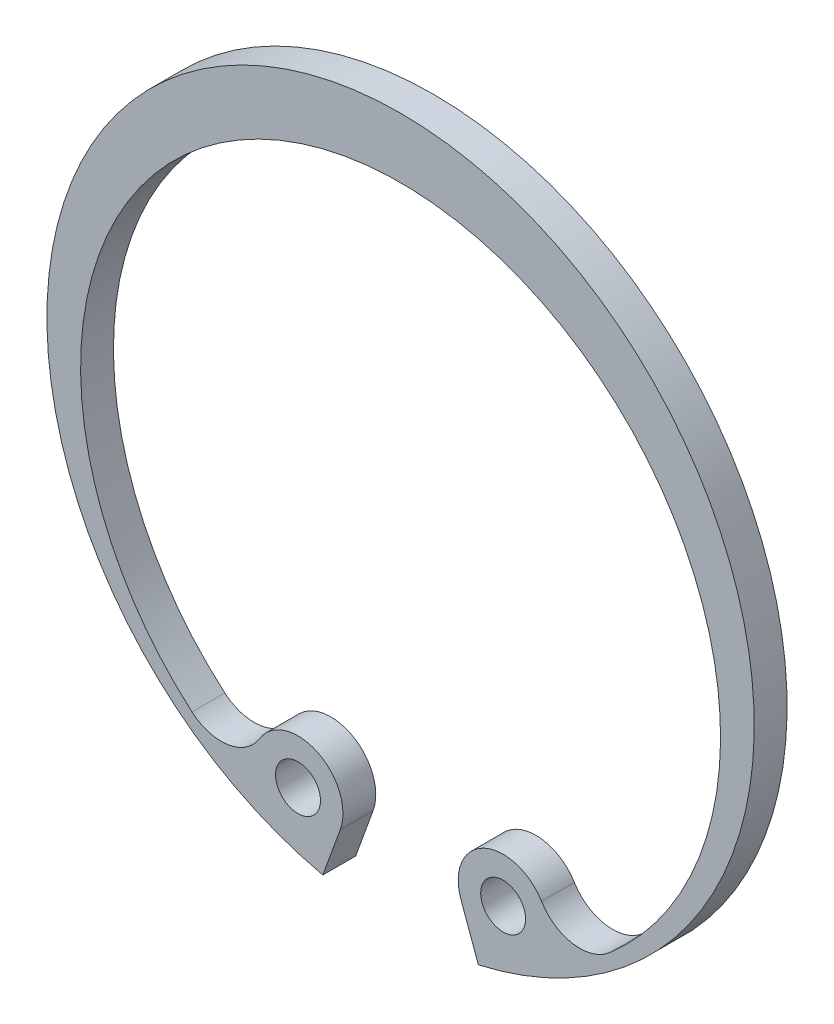
SolidWorks part; units mm, degrees
ref_plane "Front" through (0, 0, 0) normal (0, 0, 1) x (1, 0, 0)
ref_plane "Top" through (0, 0, 0) normal (0, 1, 0) x (1, 0, 0)
ref_plane "Right" through (0, 0, 0) normal (1, 0, 0) x (0, 0, -1)
ref_axis "Center Axis" through (0, 0, 1.5888) along (0, 0, -1)
sketch "Sketch1" plane through (0, 0, 0) normal (0, 0, 1) x (1, 0, 0)
  circle A0 centre (0, 0) radius 10.5
  dimension "D1" = 21
extrude "Extrude1" add sketch "Sketch1" along normal blind 0.975
ref_plane "Reference Plane for Front Recess" through (0, 0, 0.975) normal (0, 0, 1) x (1, 0, 0)
sketch "Sketch34" plane through (0, 0, 0.975) normal (0, 0, 1) x (1, 0, 0)
  line L0 (0, 0) -> (0, -10.6398) construction
  line L1 (0, 0) -> (-3.8763, -10.6501) construction
  line L2 (0, 0) -> (3.8763, -10.6501) construction
  line L3 (-1.7918, -8.8213) -> (-2.3092, -10.2429)
  line L4 (1.7918, -8.8213) -> (2.3092, -10.2429)
  circle A1 centre (0, 0) radius 10.5 construction
  arc A2 (2.3092, -10.2429) -> (-2.3092, -10.2429) centre (0, 0) ccw
  circle A3 centre (0, -0.7874) radius 8.1667 construction
  circle A4 centre (3.0447, -8.3653) radius 0.6667
  circle A5 centre (-3.0447, -8.3653) radius 0.6667
  arc A6 (-1.7918, -8.8213) -> (-4.1842, -7.6729) centre (-3.0447, -8.3653) ccw
  arc A7 (1.7918, -8.8213) -> (4.1842, -7.6729) centre (3.0447, -8.3653) cw
  arc A9 (-6.1928, -7.9915) -> (-4.1842, -7.6729) centre (-5.3236, -6.9804) ccw
  arc A12 (6.1928, -7.9915) -> (4.1842, -7.6729) centre (5.3236, -6.9804) cw
  arc A14 (6.1928, -7.9915) -> (-6.1928, -7.9915) centre (0, -0.7874) ccw
  point P0 (0, -0.7874)
  dimension "D2" = 2.6667
  dimension "D5" = 1.3333
  dimension "D4" = 19
  dimension "D1" = 0.7874
  dimension "D3" = 40
extrude "056-250 Snap Ring" add sketch "Sketch34" along normal blind 0.975
sketch "Sketch35" plane through (0, 0, 0) normal (0, 0, -1) x (-1, 0, 0)
  circle A1 centre (0, 0) radius 10.5
  circle A2 centre (0, 0) radius 10.5
  dimension "D1" = 0
extrude "Cut-Extrude1" cut sketch "Sketch35" against normal blind 0.975
